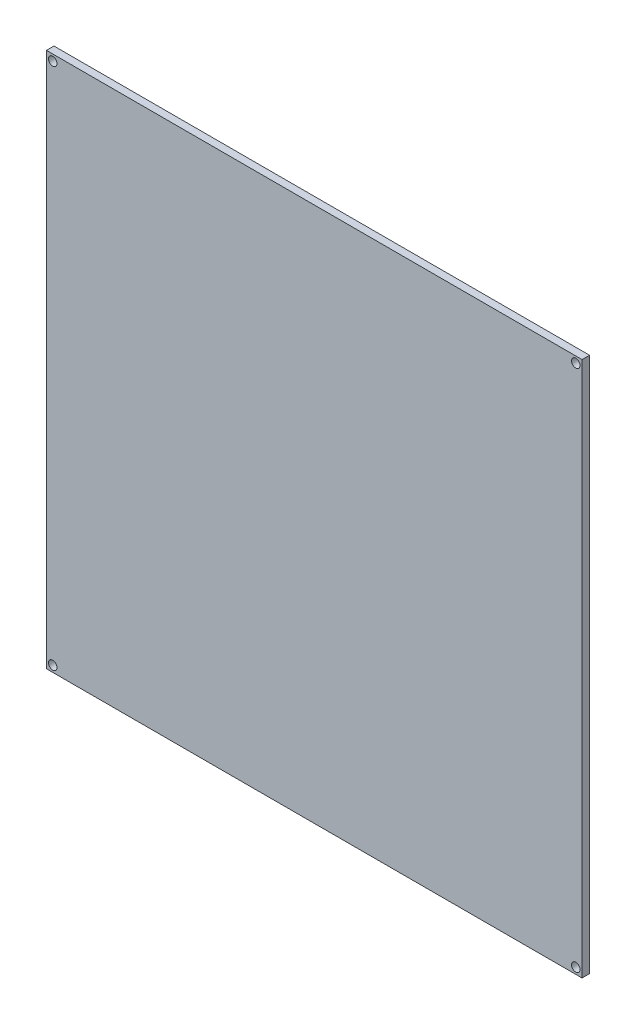
SolidWorks part; units mm, degrees
material "A-Fibra di vetro"
ref_plane "Piano frontale" through (0, 0, 0) normal (0, 0, 1) x (1, 0, 0)
ref_plane "Piano superiore" through (0, 0, 0) normal (0, 1, 0) x (1, 0, 0)
ref_plane "Piano destro" through (0, 0, 0) normal (1, 0, 0) x (0, 0, -1)
sketch "Schizzo1" plane through (0, 0, 0) normal (0, 0, 1) x (1, 0, 0)
  line L0 (-214, 214) -> (0, 0) construction
  line L1 (0, 0) -> (-214, 0)
  line L2 (0, 0) -> (0, 214)
  line L3 (0, 214) -> (-214, 214)
  line L4 (-214, 0) -> (-214, 214)
  line L5 (-214, 0) -> (0, 214) construction
  dimension "D1" = 214
  dimension "D2" = 214
extrude "Estrusione-Estrusione1" add sketch "Schizzo1" against normal blind 3
hole_wizard "Foro per Vite M3-1" positions "Schizzo3" profile "Schizzo2" hole size "M3" standard "ISO" end condition up to next
sketch "Schizzo3" plane through (0, 0, 0) normal (0, 0, 1) x (1, 0, 0)
  line L0 (0, 214) -> (-214, 0) construction
  line L2 (0, 0) -> (-214, 214) construction
  point P0 (-2.5, 211.5)
  point P2 (-2.5, 2.5)
  point P4 (-211.5, 211.5)
  point P6 (-211.5, 2.5)
  dimension "D1" = 209
  dimension "D2" = 209
sketch "Schizzo2" plane through (-2.5, 211.5, 0) normal (1, 0, 0) x (0, -1, 0)
  line L0 (0, 0) -> (0, 3)
  line L1 (0, 3) -> (1.7, 3)
  line L2 (1.7, 3) -> (1.7, 0)
  line L5 (1.7, 0) -> (0, 0)
  line L11 (0, -6.35) -> (0, 107.95) construction
  dimension "Thru Hole Dia." = 3.4
  dimension "Thru Hole Depth" = 3
